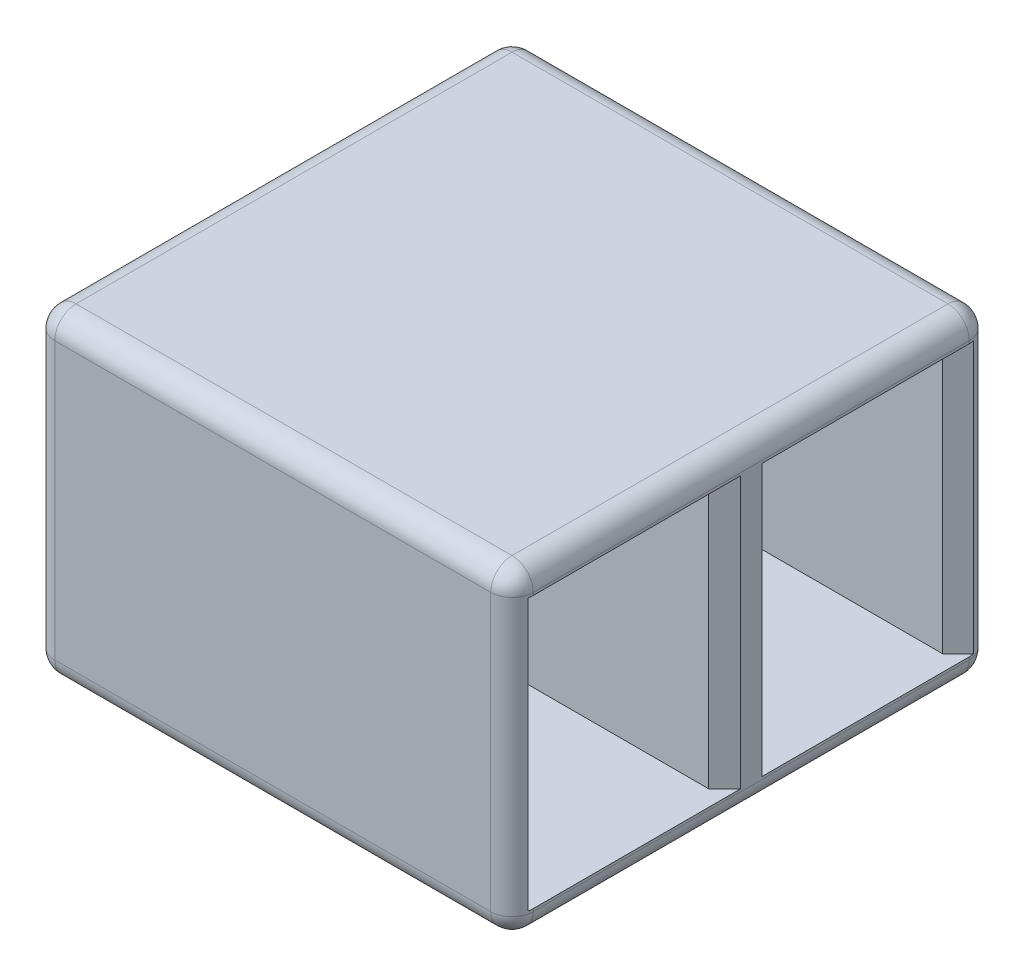
SolidWorks part; units mm, degrees
material "Custom Plastic"
ref_plane "Front Plane" through (0, 0, 0) normal (0, 0, 1) x (1, 0, 0)
ref_plane "Top Plane" through (0, 0, 0) normal (0, 1, 0) x (1, 0, 0)
ref_plane "Right Plane" through (0, 0, 0) normal (1, 0, 0) x (0, 0, -1)
sketch "Sketch1" plane through (0, 0, 0) normal (0, 1, 0) x (1, 0, 0)
  line L1 (-22.5, -22.5) -> (22.5, -22.5)
  line L2 (-22.5, -22.5) -> (-22.5, 22.5)
  line L3 (-22.5, 22.5) -> (22.5, 22.5)
  line L4 (22.5, -22.5) -> (22.5, 22.5)
  line L5 (-22.5, -22.5) -> (22.5, 22.5) construction
  line L6 (-22.5, 22.5) -> (22.5, -22.5) construction
  point P0 (0, 0)
  dimension "D1" = 45
  dimension "D2" = 45
extrude "Boss-Extrude1" add sketch "Sketch1" along normal blind 15 and the other way blind 15 contours L2 L3 L4 L1
sketch "Sketch2" plane through (0, 0, 0) normal (0, 1, 0) x (1, 0, 0)
  line L0 (-1000, 0) -> (49000, 0) construction
  line L1 (22.5, -22.5) -> (22.5, 22.5) construction
  line L2 (22.5, 19.5) -> (-15.5, 19.5)
  line L3 (22.5, 19.5) -> (22.5, 2.5)
  line L4 (22.5, 2.5) -> (-15.5, 2.5)
  line L5 (-15.5, 19.5) -> (-15.5, 2.5)
  line L6 (-15.5, -19.5) -> (-15.5, -2.5)
  line L7 (22.5, -2.5) -> (-15.5, -2.5)
  line L8 (22.5, -19.5) -> (22.5, -2.5)
  line L9 (22.5, -19.5) -> (-15.5, -19.5)
  dimension "D1" = 17
  dimension "D2" = 38
  dimension "D3" = 5
extrude "Cut-Extrude1" cut sketch "Sketch2" against normal blind 12.75 and the other way blind 12.75
fillet "Fillet1" radius 13 4 edges at (-15.5, -12.75, -11) (-15.5, 12.75, -11) (-15.5, 12.75, 11) (-15.5, -12.75, 11)
fillet "Fillet2" radius 2 12 edges at (-22.5, -15, 0) (-22.5, 0, -22.5) (-22.5, 15, 0) (-22.5, 0, 22.5) (22.5, 0, -22.5) (22.5, 0, 22.5) (0, -15, 22.5) (22.5, -15, 0) (0, -15, -22.5) (0, 15, -22.5) (0, 15, 22.5) (22.5, 15, 0)
sketch "Sketch3" plane through (0, 0, 0) normal (0, 1, 0) x (1, 0, 0)
  line L0 (-22.5, 0) -> (-32.5, 0)
  line L1 (-22.5, -20.5) -> (-22.5, 20.5) construction
  line L2 (-32.5, 0) -> (-22.5, 5)
  line L3 (-22.5, 5) -> (-22.5, 0)
  dimension "D1" = 5
  dimension "D2" = 10
revolve "Revolve1" add sketch "Sketch3" angle 360 about L0
chamfer "Chamfer3" distance 1.5 angle 45 4 edges at (22.5, 0, -19.5) (22.5, 0, -2.5) (22.5, 0, 2.5) (22.5, 0, 19.5)
